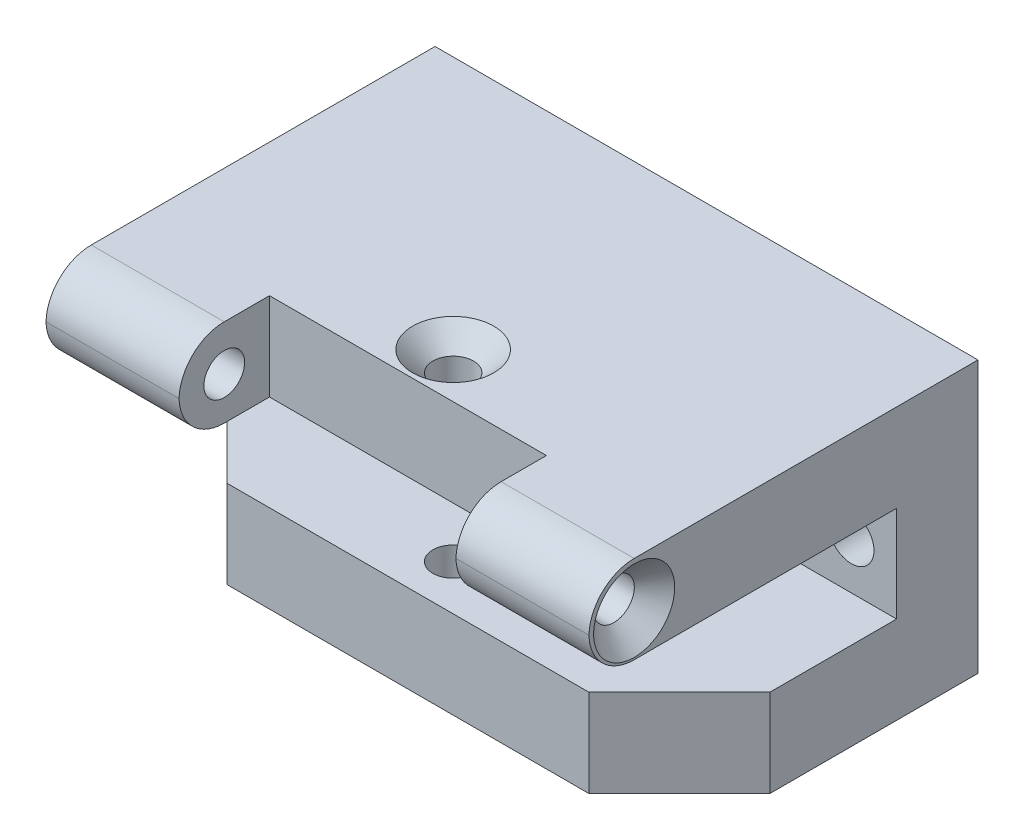
SolidWorks part; units mm, degrees
ref_plane "Front Plane" through (0, 0, 0) normal (0, 0, 1) x (1, 0, 0)
ref_plane "Top Plane" through (0, 0, 0) normal (0, 1, 0) x (1, 0, 0)
ref_plane "Right Plane" through (0, 0, 0) normal (1, 0, 0) x (0, 0, -1)
sketch "Sketch1" plane through (0, 0, 0) normal (0, 0, 1) x (1, 0, 0)
  line L1 (-30, -15) -> (30, -15)
  line L2 (-30, -15) -> (-30, 15)
  line L3 (-30, 15) -> (30, 15)
  line L4 (30, -15) -> (30, 15)
  line L5 (-30, -15) -> (30, 15) construction
  line L6 (-30, 15) -> (30, -15) construction
  point P0 (0, 0)
  dimension "D1" = 60
  dimension "D2" = 30
extrude "Boss-Extrude1" add sketch "Sketch1" along normal blind 9
sketch "Sketch2" plane through (0, 0, 9) normal (0, 0, 1) x (1, 0, 0)
  line L1 (-30, 5.3) -> (30, 5.3)
  line L2 (-30, 5.3) -> (-30, 15)
  line L3 (-30, 15) -> (30, 15)
  line L4 (30, 5.3) -> (30, 15)
  line L5 (-30, 5.3) -> (30, 15) construction
  line L6 (-30, 15) -> (30, 5.3) construction
  line L7 (-30, -5.3) -> (30, -5.3)
  line L8 (-30, -5.3) -> (-30, -15)
  line L9 (-30, -15) -> (30, -15)
  line L10 (30, -5.3) -> (30, -15)
  line L11 (-30, -5.3) -> (30, -15) construction
  line L12 (-30, -15) -> (30, -5.3) construction
  point P0 (0, 10.15)
  point P8 (0, -10.15)
  dimension "D1" = 9.7
  dimension "D2" = 9.7
extrude "Boss-Extrude2" add sketch "Sketch2" along normal blind 24
chamfer "Chamfer1" distance 10 angle 45 2 edges at (-30, -10.15, 33) (30, -10.15, 33)
hole_wizard "CSK for M4 SFHCS1" positions "Sketch3" profile "Sketch4" countersink size "M4" standard "ANSI Metric"
sketch "Sketch3" plane through (0, -15, 0) normal (0, -1, 0) x (-1, 0, 0)
  line L0 (20, -33) -> (-20, -33) construction
  point P0 (0, -28)
  dimension "D1" = 5
sketch "Sketch4" plane through (0, -15, 28) normal (1, 0, 0) x (0, 0, -1)
  line L0 (0, 0) -> (0, 13.3519)
  line L1 (0, 13.3519) -> (2.25, 12)
  line L2 (2.25, 12) -> (2.25, 2.23)
  line L3 (2.25, 2.23) -> (4.48, 0)
  line L5 (4.48, 0) -> (0, 0)
  line L6 (-2.25, 2.23) -> (-4.48, 0) construction
  line L10 (0, 13.3519) -> (-2.25, 12) construction
  line L11 (0, -6.35) -> (0, 107.95) construction
  dimension "Hole Dia." = 4.5
  dimension "Hole Depth" = 12
  dimension "Near C'Sink Dia." = 8.96
  dimension "Near C'Sink Angle" = 90
  dimension "Drill Angle" = 118
hole_wizard "CSK for M4 SFHCS3" positions "Sketch5" profile "Sketch6" countersink size "M4" standard "ANSI Metric"
sketch "Sketch5" plane through (0, 15, 0) normal (0, 1, 0) x (1, 0, 0)
  circle A0 centre (0, -28) radius 2.25 construction
  circle A1 centre (0, -28) radius 2.25
  point P1 (0, -28)
sketch "Sketch6" plane through (0, 15, 28) normal (1, 0, 0) x (0, 0, 1)
  line L0 (0, 0) -> (0, 13.3519)
  line L1 (0, 13.3519) -> (2.25, 12)
  line L2 (2.25, 12) -> (2.25, 2.23)
  line L3 (2.25, 2.23) -> (4.48, 0)
  line L5 (4.48, 0) -> (0, 0)
  line L6 (-2.25, 2.23) -> (-4.48, 0) construction
  line L10 (0, 13.3519) -> (-2.25, 12) construction
  line L11 (0, -6.35) -> (0, 107.95) construction
  dimension "Hole Dia." = 4.5
  dimension "Hole Depth" = 12
  dimension "Near C'Sink Dia." = 8.96
  dimension "Near C'Sink Angle" = 90
  dimension "Drill Angle" = 118
hole_wizard "CBORE for M5 Hex Head Bolt2" positions "Sketch7" profile "Sketch8" counterbore size "M5" standard "ANSI Metric"
sketch "Sketch7" plane through (0, 0, 9) normal (0, 0, 1) x (1, 0, 0)
  line L0 (-25, 0) -> (25, 0)
  point P1 (-25, 0)
  point P2 (25, 0)
  dimension "D1" = 50
sketch "Sketch8" plane through (-25, 0, 9) normal (1, 0, 0) x (0, -1, 0)
  line L0 (0, 0) -> (0, 13.3519)
  line L1 (0, 13.3519) -> (2.25, 12)
  line L2 (2.25, 12) -> (2.25, 4.2)
  line L3 (2.25, 4.2) -> (2.5, 4.2)
  line L4 (2.5, 4.2) -> (2.5, 0)
  line L5 (2.5, 0) -> (0, 0)
  line L10 (0, 13.3519) -> (-2.25, 12) construction
  line L11 (0, -6.35) -> (0, 107.95) construction
  dimension "Hole Dia." = 4.5
  dimension "Hole Depth" = 12
  dimension "C'Bore Dia." = 5
  dimension "C'Bore Depth" = 4.2
  dimension "Drill Angle" = 118
sketch "Sketch9" plane through (0, 0, 33) normal (0, 0, 1) x (1, 0, 0)
  line L0 (-30, 5.3) -> (30, 5.3) construction
  line L1 (-30, 15) -> (-15.3, 15)
  line L2 (-30, 15) -> (-30, 5.3)
  line L3 (-30, 5.3) -> (-15.3, 5.3)
  line L4 (-15.3, 15) -> (-15.3, 5.3)
  dimension "D1" = 14.7
extrude "Boss-Extrude3" add sketch "Sketch9" along normal blind 10
hole_wizard "CSK for M4 SFHCS2" positions "Sketch10" profile "Sketch11" countersink size "M4" standard "ANSI Metric" end condition up to next
sketch "Sketch10" plane through (-30, 0, 0) normal (-1, 0, 0) x (0, 0, 1)
  line L0 (43, 15) -> (43, 5.3) construction
  line L1 (43, 15) -> (0, 15) construction
  point P0 (38, 10)
  dimension "D1" = 5
  dimension "D2" = 5
sketch "Sketch11" plane through (-30, 10, 38) normal (0, 1, 0) x (0, 0, 1)
  line L0 (0, 0) -> (0, 14.7)
  line L1 (0, 14.7) -> (2.25, 14.7)
  line L2 (2.25, 14.7) -> (2.25, 2.23)
  line L3 (2.25, 2.23) -> (4.48, 0)
  line L5 (4.48, 0) -> (0, 0)
  line L6 (-2.25, 2.23) -> (-4.48, 0) construction
  line L11 (0, -6.35) -> (0, 107.95) construction
  dimension "Thru Hole Dia." = 4.5
  dimension "Thru Hole Depth" = 14.7
  dimension "Near C'Sink Dia." = 8.96
  dimension "Near C'Sink Angle" = 90
mirror "Mirror1" about plane through (0, 0, 0) normal (1, 0, 0) of "CSK for M4 SFHCS2", "Boss-Extrude3"
fillet "Fillet1" radius 5 4 edges at (22.65, 5.3, 43) (22.65, 15, 43) (-22.65, 5.3, 43) (-22.65, 15, 43)
